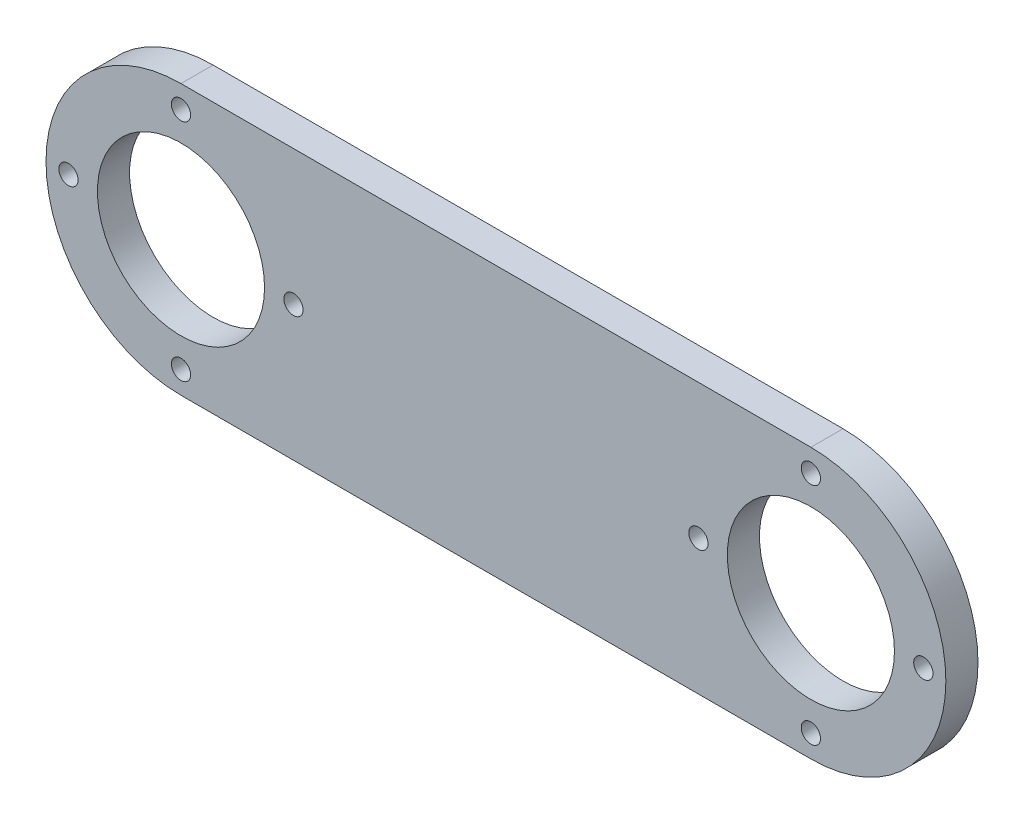
SolidWorks part; units mm, degrees
material "Thornel Mat VMA"
ref_plane "Front Plane" through (0, 0, 0) normal (0, 0, 1) x (1, 0, 0)
ref_plane "Top Plane" through (0, 0, 0) normal (0, 1, 0) x (1, 0, 0)
ref_plane "Right Plane" through (0, 0, 0) normal (1, 0, 0) x (0, 0, -1)
sketch "Sketch1" plane through (0, 0, 0) normal (0, 0, 1) x (1, 0, 0)
  line L0 (49, 26) -> (-49, 26) construction
  line L1 (-49, -16) -> (49, -16) construction
  line L2 (49, 26) -> (-49, 26)
  line L3 (-49, -16) -> (49, -16)
  circle A0 centre (49, 5) radius 21 construction
  circle A2 centre (-49, 5) radius 13 construction
  circle A3 centre (-66.5, 5) radius 1.5 construction
  circle A4 centre (-49, 22.5) radius 1.5 construction
  circle A5 centre (-31.5, 5) radius 1.5 construction
  circle A6 centre (-49, -12.5) radius 1.5 construction
  circle A7 centre (49, 5) radius 13 construction
  circle A8 centre (31.5, 5) radius 1.5 construction
  circle A9 centre (49, 22.5) radius 1.5 construction
  circle A10 centre (66.5, 5) radius 1.5 construction
  circle A11 centre (49, -12.5) radius 1.5 construction
  arc A12 (49, -16) -> (49, 26) centre (49, 5) ccw
  circle A14 centre (-49, 5) radius 13
  circle A15 centre (-66.5, 5) radius 1.5
  circle A16 centre (-49, 22.5) radius 1.5
  circle A17 centre (-31.5, 5) radius 1.5
  circle A18 centre (-49, -12.5) radius 1.5
  circle A19 centre (49, 5) radius 13
  circle A20 centre (31.5, 5) radius 1.5
  circle A21 centre (49, 22.5) radius 1.5
  circle A22 centre (66.5, 5) radius 1.5
  circle A23 centre (49, -12.5) radius 1.5
  arc A24 (-49, 26) -> (-49, -16) centre (-49, 5) ccw
extrude "Boss-Extrude1" add sketch "Sketch1" along normal blind 5
